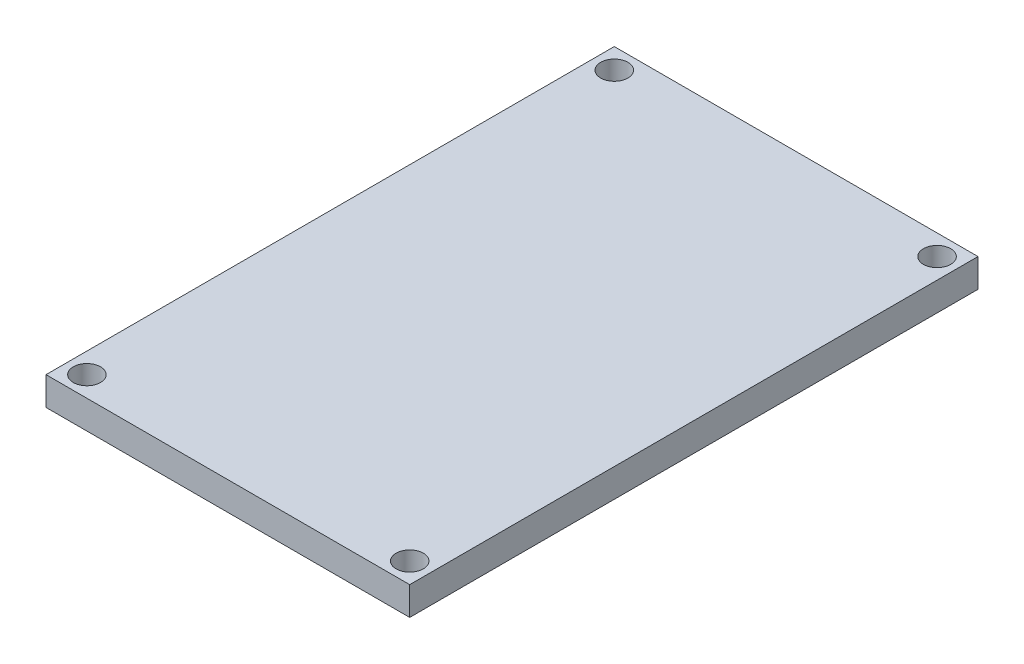
SolidWorks part; units mm, degrees
ref_plane "Front Plane" through (0, 0, 0) normal (0, 0, 1) x (1, 0, 0)
ref_plane "Top Plane" through (0, 0, 0) normal (0, 1, 0) x (1, 0, 0)
ref_plane "Right Plane" through (0, 0, 0) normal (1, 0, 0) x (0, 0, -1)
sketch "Sketch1" plane through (0, 0, 0) normal (0, 1, 0) x (1, 0, 0)
  line L1 (0, 0) -> (40.64, 0)
  line L2 (0, 0) -> (0, 63.5)
  line L3 (0, 63.5) -> (40.64, 63.5)
  line L4 (40.64, 0) -> (40.64, 63.5)
  circle A0 centre (2.286, 61.214) radius 1.524
  circle A1 centre (38.354, 61.214) radius 1.524
  circle A2 centre (2.286, 2.286) radius 1.524
  circle A3 centre (38.354, 2.286) radius 1.524
  dimension "D3" = 40.64
  dimension "D4" = 2.286
  dimension "D5" = 2.286
  dimension "D6" = 2.286
  dimension "D7" = 2.286
  dimension "D8" = 2.286
  dimension "D9" = 2.286
  dimension "D10" = 2.286
  dimension "D11" = 2.286
  dimension "D1" = 3.048
  dimension "D2" = 63.5
extrude "Boss-Extrude1" add sketch "Sketch1" along normal blind 3.175 contours L1 L4 L3 L2 A3 A2 A1 A0 region at (20.32, 0, -31.75)
